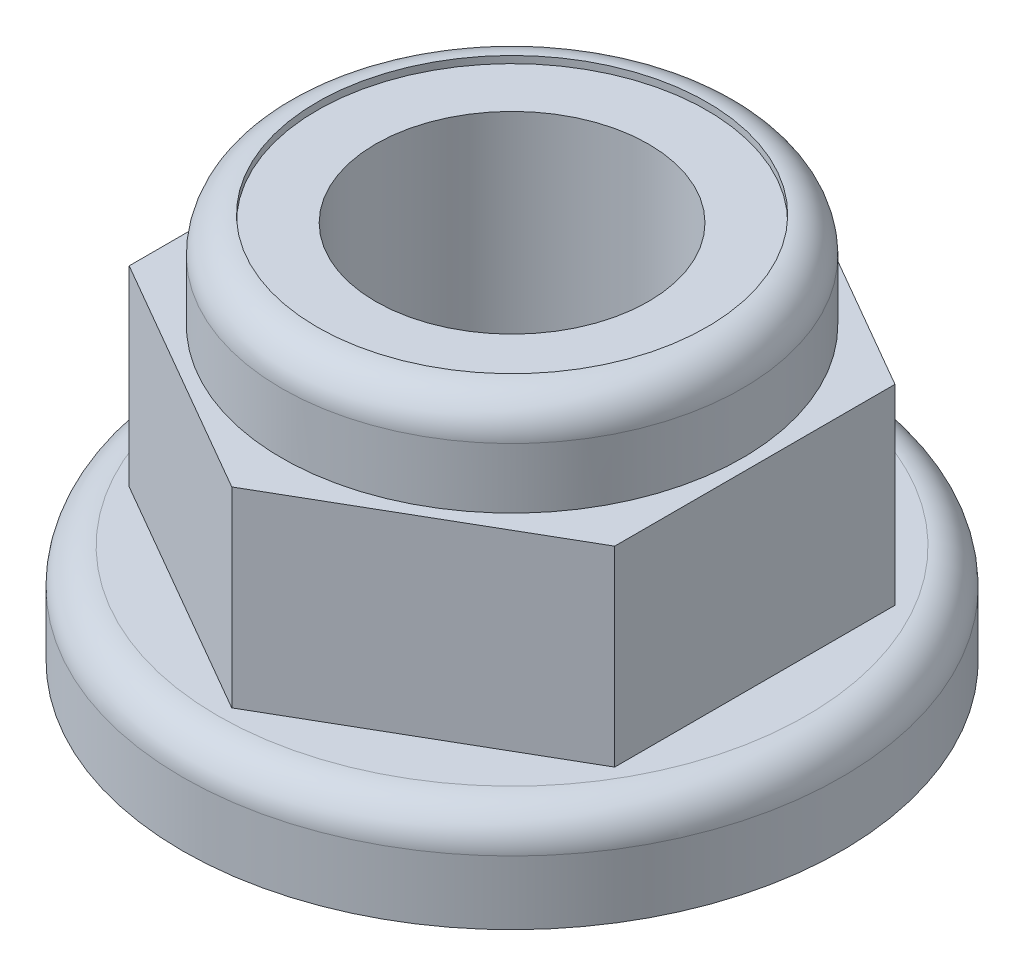
SolidWorks part; units mm, degrees
ref_plane "Front Plane" through (0, 0, 0) normal (0, 0, 1) x (1, 0, 0)
ref_plane "Top Plane" through (0, 0, 0) normal (0, 1, 0) x (1, 0, 0)
ref_plane "Right Plane" through (0, 0, 0) normal (1, 0, 0) x (0, 0, -1)
sketch "Sketch1" plane through (0, 0, 0) normal (0, 1, 0) x (1, 0, 0)
  circle A0 centre (0, 0) radius 4.65
  dimension "D1" = 9.3
extrude "Boss-Extrude1" add sketch "Sketch1" along normal blind 1.4
sketch "Sketch2" plane through (0, 1.4, 0) normal (0, 1, 0) x (1, 0, 0)
  line L1 (0, -3.9548) -> (3.425, -1.9774)
  line L2 (3.425, -1.9774) -> (3.425, 1.9774)
  line L3 (3.425, 1.9774) -> (0, 3.9548)
  line L4 (0, 3.9548) -> (-3.425, 1.9774)
  line L5 (-3.425, 1.9774) -> (-3.425, -1.9774)
  line L6 (-3.425, -1.9774) -> (0, -3.9548)
  circle A0 centre (0, 0) radius 3.425 construction
  dimension "D1" = 6.85
extrude "Boss-Extrude2" add sketch "Sketch2" along normal blind 2.7
sketch "Sketch3" plane through (0, 4.1, 0) normal (0, 1, 0) x (1, 0, 0)
  circle A0 centre (0, 0) radius 3.25
  dimension "D1" = 6.5
extrude "Boss-Extrude3" add sketch "Sketch3" along normal blind 1.35
fillet "Fillet1" radius 0.5 2 edges at (0, 5.45, 3.25) (0, 1.4, 4.65)
sketch "Sketch7" plane through (0, 5.45, 0) normal (0, 1, 0) x (1, 0, 0)
  circle A0 centre (0, 0) radius 1.925
  dimension "D1" = 3.85
extrude "Cut-Extrude1" cut sketch "Sketch7" against normal up to next
sketch "Sketch8" plane through (0, 5.45, 0) normal (0, 1, 0) x (1, 0, 0)
  circle A0 centre (0, 0) radius 1.925 construction
  circle A1 centre (0, 0) radius 2.75
  circle A2 centre (0, 0) radius 2.75
  circle A3 centre (0, 0) radius 1.925
  dimension "D1" = 0
extrude "Cut-Extrude2" cut sketch "Sketch8" against normal blind 0.1
